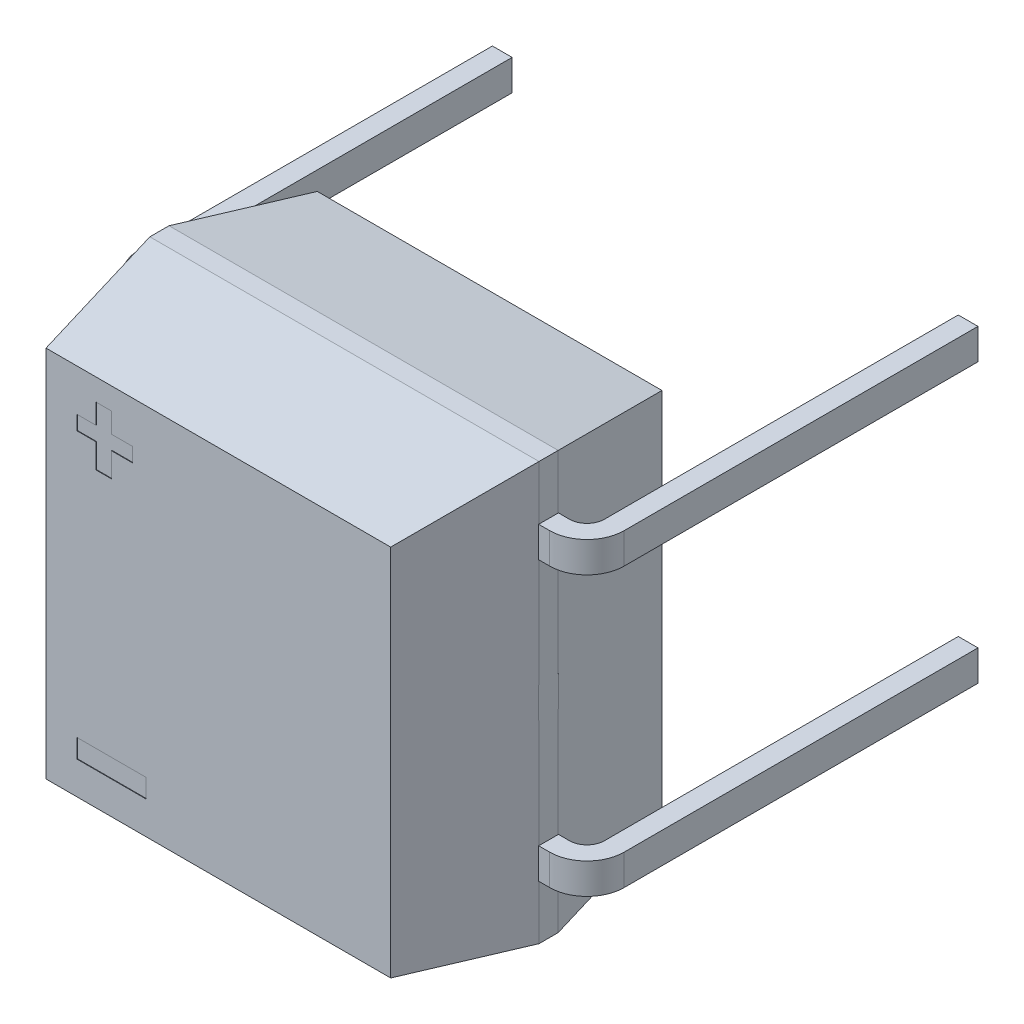
SolidWorks part; units mm, degrees
note: The reader was unsure of these and kept them because the rebuilt part matched: shared geometry of "Эскиз5<2>".
ref_plane "Front" through (0, 0, 0) normal (0, 0, 1) x (1, 0, 0)
ref_plane "Top" through (0, 0, 0) normal (0, 1, 0) x (1, 0, 0)
ref_plane "Right" through (0, 0, 0) normal (1, 0, 0) x (0, 0, -1)
sketch "Эскиз1" plane through (0, 0, 0) normal (0, 0, 1) x (1, 0, 0)
  line L1 (-0.8, -8.42) -> (0.8, -8.42)
  line L2 (-0.8, -8.42) -> (-0.8, -6.82)
  line L3 (-0.8, -6.82) -> (0.8, -6.82)
  line L4 (0.8, -8.42) -> (0.8, -6.82)
  line L5 (-0.8, -5.88) -> (0.8, -5.88)
  line L6 (-0.8, -5.88) -> (-0.8, -4.28)
  line L7 (-0.8, -4.28) -> (0.8, -4.28)
  line L8 (0.8, -5.88) -> (0.8, -4.28)
  line L9 (-0.8, -3.34) -> (0.8, -3.34)
  line L10 (-0.8, -3.34) -> (-0.8, -1.74)
  line L11 (-0.8, -1.74) -> (0.8, -1.74)
  line L12 (0.8, -3.34) -> (0.8, -1.74)
  line L13 (-0.8, -0.8) -> (0.8, -0.8)
  line L14 (-0.8, -0.8) -> (-0.8, 0.8)
  line L15 (-0.8, 0.8) -> (0.8, 0.8)
  line L16 (0.8, -0.8) -> (0.8, 0.8)
  line L17 (7.7, -8.42) -> (9.3, -8.42)
  line L18 (7.7, -8.42) -> (7.7, -6.82)
  line L19 (7.7, -6.82) -> (9.3, -6.82)
  line L20 (9.3, -8.42) -> (9.3, -6.82)
  line L21 (7.7, -5.88) -> (9.3, -5.88)
  line L22 (7.7, -5.88) -> (7.7, -4.28)
  line L23 (7.7, -4.28) -> (9.3, -4.28)
  line L24 (9.3, -5.88) -> (9.3, -4.28)
  line L25 (7.7, -3.34) -> (9.3, -3.34)
  line L26 (7.7, -3.34) -> (7.7, -1.74)
  line L27 (7.7, -1.74) -> (9.3, -1.74)
  line L28 (9.3, -3.34) -> (9.3, -1.74)
  line L29 (7.7, -0.8) -> (9.3, -0.8)
  line L30 (7.7, -0.8) -> (7.7, 0.8)
  line L31 (7.7, 0.8) -> (9.3, 0.8)
  line L32 (9.3, -0.8) -> (9.3, 0.8)
ref_plane "Плоскость1" through (0, 0, 5.33) normal (0, 0, 1) x (1, 0, 0)
sketch "Эскиз3" plane through (0, 0, 5.33) normal (0, 0, 1) x (1, 0, 0)
  line L0 (0.7, 1.27) -> (4.25, 1.27)
  line L1 (4.25, 1.27) -> (7.8, 1.27)
  line L2 (0.7, -8.89) -> (0.7, 1.27)
  line L3 (7.8, 1.27) -> (7.8, -8.89)
  line L4 (7.8, -8.89) -> (0.7, -8.89)
  line L5 (4.25, -8.89) -> (4.25, 1.27) construction
  dimension "D1" = 10.16
  dimension "D2" = 7.1
  dimension "D3" = 0.7
  dimension "D4" = 8.89
extrude "Вытянуть1" add sketch "Эскиз3" against normal blind 4.95
sketch "Эскиз4" plane through (0, 0, 0) normal (0, 1, 0) x (1, 0, 0)
  line L0 (0, 0) -> (0, -2.355)
  line L1 (0.5, -2.855) -> (0.7, -2.855)
  line L2 (0.7, -0.38) -> (0.7, -5.33) construction
  line L3 (4.25, -0.38) -> (4.25, -5.33) construction
  line L4 (7.8, -0.38) -> (0.7, -0.38) construction
  line L5 (7.8, -5.33) -> (0.7, -5.33) construction
  line L6 (8, -2.855) -> (7.8, -2.855)
  line L7 (8.5, 0) -> (8.5, -2.355)
  line L8 (0.7, -2.855) -> (7.8, -2.855)
  line L9 (8.5, 0) -> (8.5, 4.1)
  arc A0 (0, -2.355) -> (0.5, -2.855) centre (0.5, -2.355) ccw
  arc A1 (8, -2.855) -> (8.5, -2.355) centre (8, -2.355) ccw
  point P18 (0, -2.855)
  point P21 (8.5, -2.855)
  dimension "D2" = 0.5
  dimension "D1" = 4.1
sketch "Эскиз5" plane through (0, 0, 0) normal (0, 0, 1) x (1, 0, 0)
  line L0 (0.18, -2.26) -> (-0.18, -2.26)
  line L1 (0.18, 0.28) -> (-0.18, 0.28)
  line L2 (0.18, 0.28) -> (0.18, -0.28)
  line L3 (0.18, -0.28) -> (-0.18, -0.28)
  line L4 (-0.18, 0.28) -> (-0.18, -0.28)
  line L5 (0.18, -2.26) -> (0.18, -2.82)
  line L6 (0.18, -2.82) -> (-0.18, -2.82)
  line L7 (-0.18, -2.26) -> (-0.18, -2.82)
  line L8 (0.18, -4.8) -> (-0.18, -4.8)
  line L9 (0.18, -4.8) -> (0.18, -5.36)
  line L10 (0.18, -5.36) -> (-0.18, -5.36)
  line L11 (-0.18, -4.8) -> (-0.18, -5.36)
  line L12 (0.18, -7.34) -> (-0.18, -7.34)
  line L13 (0.18, -7.34) -> (0.18, -7.9)
  line L14 (0.18, -7.9) -> (-0.18, -7.9)
  line L15 (-0.18, -7.34) -> (-0.18, -7.9)
  dimension "D1" = 0.36
  dimension "D2" = 0.18
  dimension "D3" = 0.28
  dimension "D4" = 0.56
  dimension "D5" = 2.54
sweep "По траектории1" add profiles "Эскиз5" path "Эскиз4"
extrude "Вытянуть2" add sketch "Эскиз5<2>" against normal blind 4.1
sketch "Эскиз5<2>" plane through (0, 0, 0) normal (0, 0, 1) x (1, 0, 0) same geometry as "Эскиз5"
chamfer "Фаска1" distance 2.3 angle 10 8 edges at (4.25, -8.89, 0.38) (7.8, -3.81, 0.38) (4.25, 1.27, 0.38) (0.7, -3.81, 0.38) (4.25, 1.27, 5.33) (7.8, -3.81, 5.33) (4.25, -8.89, 5.33) (0.7, -3.81, 5.33)
sketch "Эскиз6" plane through (0, 0, 5.33) normal (0, 0, 1) x (1, 0, 0)
  line L1 (2.3007, 0.1004) -> (2.684, 0.1004)
  line L2 (1.6727, -5.3479) -> (2.9287, -5.3479)
  line L3 (1.6727, -5.3479) -> (1.6727, -5.0053)
  line L4 (1.6727, -5.0053) -> (2.9287, -5.0053)
  line L5 (2.9287, -5.3479) -> (2.9287, -5.0053)
  line L6 (1.6727, -0.1606) -> (2.0178, -0.1606)
  line L7 (1.6727, -0.1606) -> (1.6727, 0.1004)
  line L8 (1.6727, 0.1004) -> (2.0178, 0.1004)
  line L9 (2.684, -0.1606) -> (2.684, 0.1004)
  line L10 (2.0178, -0.6051) -> (2.3007, -0.6051)
  line L11 (2.0178, -0.6051) -> (2.0178, -0.1606)
  line L12 (2.0178, 0.4675) -> (2.3007, 0.4675)
  line L13 (2.3007, -0.6051) -> (2.3007, -0.1606)
  line L14 (2.0178, 0.1004) -> (2.0178, 0.4675)
  line L15 (2.3007, 0.1004) -> (2.3007, 0.4675)
  line L16 (2.3007, -0.1606) -> (2.684, -0.1606)
extrude "Вырез-Вытянуть1" cut sketch "Эскиз6" against normal blind 0.01
sketch "Эскиз7" plane through (0, 0, 5.33) normal (0, 0, 1) x (1, 0, 0)
  line L0 (7.8, -8.89) -> (0.7, -8.89) construction
  line L1 (-1.1745, -10.0023) -> (9.3817, -10.0023)
  line L2 (-1.1745, -10.0023) -> (-1.1745, -6.35)
  line L3 (-1.1745, -6.35) -> (9.3817, -6.35)
  line L4 (9.3817, -10.0023) -> (9.3817, -6.35)
  dimension "D1" = 2.54
extrude "Вырез-Вытянуть2" cut sketch "Эскиз7" against normal blind 20
chamfer "Фаска2" distance 2.3 angle 10 2 edges at (4.25, -6.35, 0.38) (4.25, -6.35, 5.33)
sketch "Эскиз8" plane through (0, 0, 5.33) normal (0, 0, 1) x (1, 0, 0)
  line L0 (7.8, -2.82) -> (7.8, -4.8) construction
  line L1 (7.8, -3.5975) -> (9.3586, -3.5975)
  line L2 (7.8, -3.5975) -> (7.8, -1.3438)
  line L3 (7.8, -1.3438) -> (9.3586, -1.3438)
  line L4 (9.3586, -3.5975) -> (9.3586, -1.3438)
  line L5 (0.7, -4.8) -> (0.7, -2.82) construction
  line L6 (0.7, -3.69) -> (-0.6505, -3.69)
  line L7 (0.7, -3.69) -> (0.7, -1.3438)
  line L8 (0.7, -1.3438) -> (-0.6505, -1.3438)
  line L9 (-0.6505, -3.69) -> (-0.6505, -1.3438)
extrude "Вырез-Вытянуть3" cut sketch "Эскиз8" against normal blind 20
sketch "Эскиз9" plane through (0, 0, -4.1) normal (0, 0, -1) x (-1, 0, 0)
  circle A0 centre (0, 0) radius 0.0934
extrude "Вырез-Вытянуть4" cut sketch "Эскиз9" against normal blind 2
